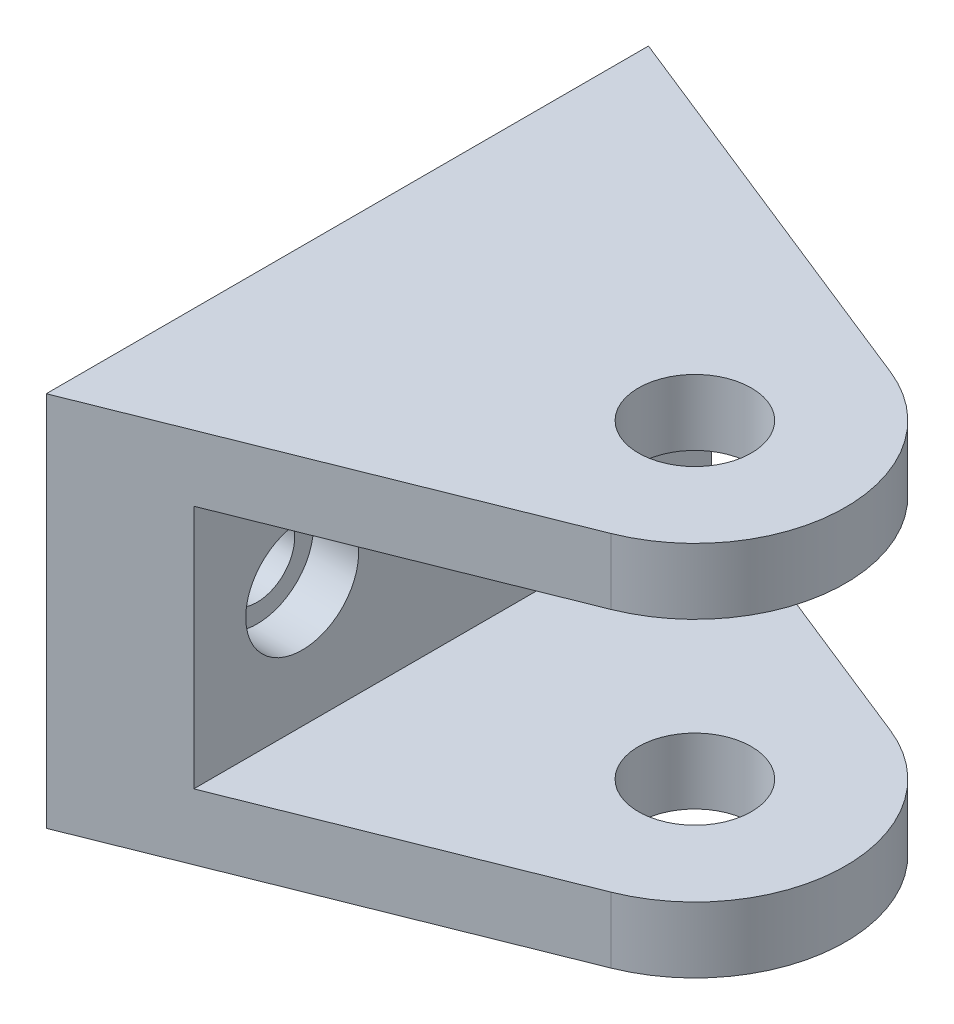
SolidWorks part; units mm, degrees
ref_plane "Front Plane" through (0, 0, 0) normal (0, 0, 1) x (1, 0, 0)
ref_plane "Top Plane" through (0, 0, 0) normal (0, 1, 0) x (1, 0, 0)
ref_plane "Right Plane" through (0, 0, 0) normal (1, 0, 0) x (0, 0, -1)
sketch "Sketch1" plane through (0, 0, 0) normal (0, 0, 1) x (1, 0, 0)
  line L0 (0, 0) -> (42.0157, 0)
  line L1 (42.0157, 0) -> (42.0157, 5.5499)
  line L2 (42.0157, 5.5499) -> (8.89, 5.5499)
  line L3 (8.89, 5.5499) -> (8.89, 26.2001)
  line L4 (8.89, 26.2001) -> (42.0157, 26.2001)
  line L5 (42.0157, 26.2001) -> (42.0157, 31.75)
  line L6 (42.0157, 31.75) -> (0, 31.75)
  line L7 (0, 31.75) -> (0, 0)
  line L8 (29.3157, 31.75) -> (29.3157, 0) construction
  dimension "D1" = 31.75
  dimension "D2" = 20.6502
  dimension "D3" = 12.7
  dimension "D4" = 8.89
extrude "Boss-Extrude1" add sketch "Sketch1" along normal blind 50.8
sketch "Sketch2" plane through (8.89, 0, 0) normal (1, 0, 0) x (0, 0, -1)
  line L0 (-25.4, 31.75) -> (-25.4, 0) construction
  line L1 (-50.8, 31.75) -> (0, 31.75) construction
  line L2 (-50.8, 0) -> (0, 0) construction
  line L3 (-38.1, 15.875) -> (-12.7, 15.875) construction
  circle A0 centre (-38.1, 15.875) radius 3.175
  circle A1 centre (-12.7, 15.875) radius 3.175
  point P8 (-25.4, 15.875)
  dimension "D2" = 6.35
  dimension "D1" = 25.4
extrude "Bolt Holes" cut sketch "Sketch2" against normal up to surface (8.89 mm away) up to face at (0, 15.875, 25.4)
sketch "Sketch5" plane through (8.89, 0, 0) normal (1, 0, 0) x (0, 0, -1)
  circle A0 centre (-38.1, 15.875) radius 4.7625
  circle A1 centre (-12.7, 15.875) radius 4.7625
  circle A2 centre (-12.7, 15.875) radius 3.175 construction
  circle A3 centre (-38.1, 15.875) radius 3.175 construction
  dimension "D1" = 9.525
extrude "Cut-Extrude2" cut sketch "Sketch5" against normal blind 3.81
sketch "Sketch3" plane through (0, 0, 0) normal (0, -1, 0) x (1, 0, 0)
  line L0 (34701.1242, 25.4) -> (-34766.6696, 25.4) construction
  circle A0 centre (29.3157, 25.4) radius 4.7625
  dimension "D1" = 9.525
extrude "Spherical Holes " cut sketch "Sketch3" against normal up to surface (31.75 mm away) up to face at (21.0078, 31.75, 25.4)
sketch "Sketch4" plane through (0, 31.75, 0) normal (0, 1, 0) x (1, 0, 0)
  line L0 (42.0157, -50.8) -> (42.0157, 0) construction
  line L1 (0, 0) -> (34.031, -13.6078)
  line L2 (0, -50.8) -> (34.031, -37.1922)
  line L5 (0, 0) -> (0, -50.8)
  arc A0 (34.031, -37.1922) -> (34.031, -13.6078) centre (29.3157, -25.4) ccw
extrude "Rounding" cut sketch "Sketch4" against normal up to surface (31.75 mm away) flip side to cut up to face at (29.3157, 0, 20.6375)
